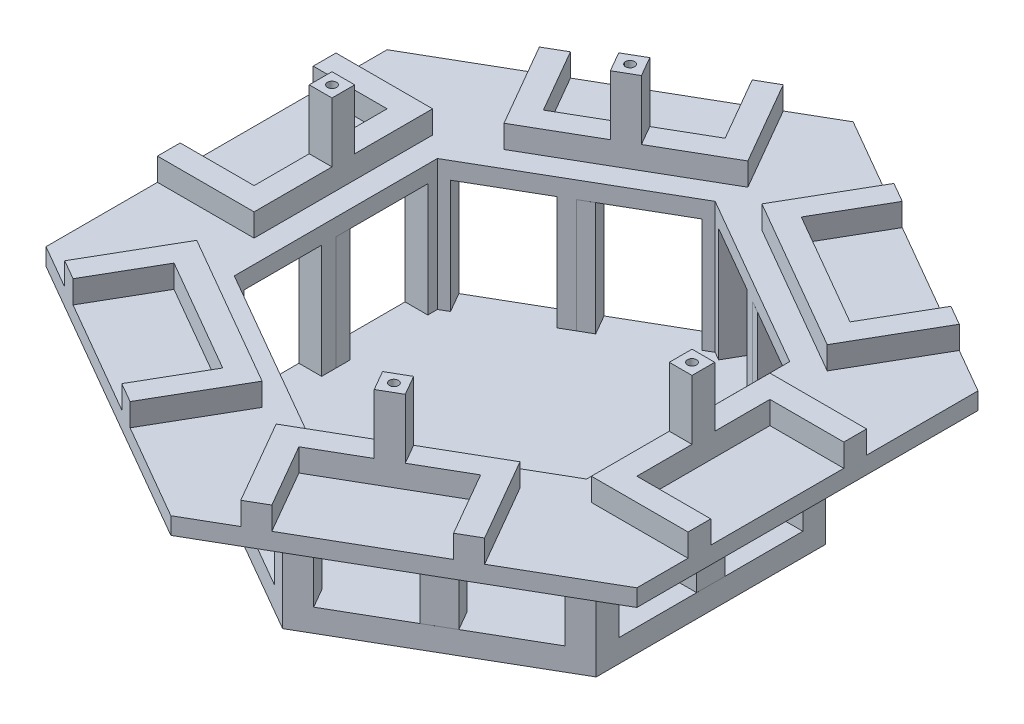
SolidWorks part; units mm, degrees
ref_plane "Front Plane" through (0, 0, 0) normal (0, 0, 1) x (1, 0, 0)
ref_plane "Top Plane" through (0, 0, 0) normal (0, 1, 0) x (1, 0, 0)
ref_plane "Right Plane" through (0, 0, 0) normal (1, 0, 0) x (0, 0, -1)
sketch "Sketch1" plane through (0, 0, 0) normal (0, 1, 0) x (1, 0, 0)
  line L1 (0, 60) -> (-51.9615, 30)
  line L2 (-51.9615, 30) -> (-51.9615, -30)
  line L3 (-51.9615, -30) -> (0, -60)
  line L4 (0, -60) -> (51.9615, -30)
  line L5 (51.9615, -30) -> (51.9615, 30)
  line L6 (51.9615, 30) -> (0, 60)
  circle A0 centre (0, 0) radius 51.9615 construction
extrude "Boss-Extrude1" add sketch "Sketch1" along normal blind 3
sketch "Sketch2" plane through (0, 3, 0) normal (0, 1, 0) x (1, 0, 0)
  line L0 (35.6673, 19.7776) -> (44.1673, 34.5)
  line L1 (51.9615, 30) -> (0, 60) construction
  line L2 (19.4808, 33.7417) -> (34.2032, 25.2417)
  line L3 (19.4808, 33.7417) -> (13.9382, 36.9417)
  line L4 (13.9382, 36.9417) -> (20.4382, 48.2)
  line L5 (34.2032, 25.2417) -> (40.7032, 36.5)
  line L7 (17.4808, 30.2776) -> (35.6673, 19.7776)
  line L8 (17.4808, 30.2776) -> (8.4741, 35.4776)
  line L9 (8.4741, 35.4776) -> (16.9741, 50.2)
  line L10 (16.9741, 50.2) -> (20.4382, 48.2)
  line L11 (40.7032, 36.5) -> (44.1673, 34.5)
  line L12 (51.9615, -17) -> (51.9615, -21)
  line L13 (34.9615, -21) -> (51.9615, -21)
  line L14 (34.9615, 0) -> (34.9615, -21)
  line L15 (34.9615, 0) -> (34.9615, 10.4)
  line L16 (34.9615, 10.4) -> (51.9615, 10.4)
  line L17 (51.9615, 10.4) -> (51.9615, 6.4)
  line L18 (38.9615, 6.4) -> (51.9615, 6.4)
  line L19 (38.9615, 0) -> (38.9615, 6.4)
  line L20 (38.9615, 0) -> (38.9615, -17)
  line L21 (38.9615, -17) -> (51.9615, -17)
  line L22 (11.2583, -53.5) -> (7.7942, -55.5)
  line L23 (-0.7058, -40.7776) -> (7.7942, -55.5)
  line L24 (17.4808, -30.2776) -> (-0.7058, -40.7776)
  line L25 (17.4808, -30.2776) -> (26.4874, -25.0776)
  line L26 (26.4874, -25.0776) -> (34.9874, -39.8)
  line L27 (34.9874, -39.8) -> (31.5233, -41.8)
  line L28 (25.0233, -30.5417) -> (31.5233, -41.8)
  line L29 (19.4808, -33.7417) -> (25.0233, -30.5417)
  line L30 (19.4808, -33.7417) -> (4.7583, -42.2417)
  line L31 (4.7583, -42.2417) -> (11.2583, -53.5)
  line L32 (-40.7032, -36.5) -> (-44.1673, -34.5)
  line L33 (-35.6673, -19.7776) -> (-44.1673, -34.5)
  line L34 (-17.4808, -30.2776) -> (-35.6673, -19.7776)
  line L35 (-17.4808, -30.2776) -> (-8.4741, -35.4776)
  line L36 (-8.4741, -35.4776) -> (-16.9741, -50.2)
  line L37 (-16.9741, -50.2) -> (-20.4382, -48.2)
  line L38 (-13.9382, -36.9417) -> (-20.4382, -48.2)
  line L39 (-19.4808, -33.7417) -> (-13.9382, -36.9417)
  line L40 (-19.4808, -33.7417) -> (-34.2032, -25.2417)
  line L41 (-34.2032, -25.2417) -> (-40.7032, -36.5)
  line L42 (-51.9615, 17) -> (-51.9615, 21)
  line L43 (-34.9615, 21) -> (-51.9615, 21)
  line L44 (-34.9615, 0) -> (-34.9615, 21)
  line L45 (-34.9615, 0) -> (-34.9615, -10.4)
  line L46 (-34.9615, -10.4) -> (-51.9615, -10.4)
  line L47 (-51.9615, -10.4) -> (-51.9615, -6.4)
  line L48 (-38.9615, -6.4) -> (-51.9615, -6.4)
  line L49 (-38.9615, 0) -> (-38.9615, -6.4)
  line L50 (-38.9615, 0) -> (-38.9615, 17)
  line L51 (-38.9615, 17) -> (-51.9615, 17)
  line L52 (-11.2583, 53.5) -> (-7.7942, 55.5)
  line L53 (0.7058, 40.7776) -> (-7.7942, 55.5)
  line L54 (-17.4808, 30.2776) -> (0.7058, 40.7776)
  line L55 (-17.4808, 30.2776) -> (-26.4874, 25.0776)
  line L56 (-26.4874, 25.0776) -> (-34.9874, 39.8)
  line L57 (-34.9874, 39.8) -> (-31.5233, 41.8)
  line L58 (-25.0233, 30.5417) -> (-31.5233, 41.8)
  line L59 (-19.4808, 33.7417) -> (-25.0233, 30.5417)
  line L60 (-19.4808, 33.7417) -> (-4.7583, 42.2417)
  line L61 (-4.7583, 42.2417) -> (-11.2583, 53.5)
  point P65 (0, 0)
  dimension "D1" = 4
  dimension "D2" = 6
extrude "Boss-Extrude2" add sketch "Sketch2" along normal blind 4
sketch "Sketch5" plane through (0, 7, 0) normal (0, 1, 0) x (1, 0, 0)
  line L18 (34.9615, -3.3) -> (34.9615, -7.3)
  line L19 (34.9615, -7.3) -> (38.9615, -7.3)
  line L20 (38.9615, -3.3) -> (38.9615, -7.3)
  line L21 (34.9615, -3.3) -> (38.9615, -3.3)
  line L22 (14.6229, -31.9276) -> (11.1588, -33.9276)
  line L23 (11.1588, -33.9276) -> (13.1588, -37.3917)
  line L24 (16.6229, -35.3917) -> (13.1588, -37.3917)
  line L25 (14.6229, -31.9276) -> (16.6229, -35.3917)
  line L30 (-34.9615, 3.3) -> (-34.9615, 7.3)
  line L31 (-34.9615, 7.3) -> (-38.9615, 7.3)
  line L32 (-38.9615, 3.3) -> (-38.9615, 7.3)
  line L33 (-34.9615, 3.3) -> (-38.9615, 3.3)
  line L34 (-14.6229, 31.9276) -> (-11.1588, 33.9276)
  line L35 (-11.1588, 33.9276) -> (-13.1588, 37.3917)
  line L36 (-16.6229, 35.3917) -> (-13.1588, 37.3917)
  line L37 (-14.6229, 31.9276) -> (-16.6229, 35.3917)
  point P31 (0, 0)
extrude "Boss-Extrude3" add sketch "Sketch5" along normal blind 10.5
sketch "Sketch7" plane through (0, 0, 0) normal (0, -1, 0) x (1, 0, 0)
  circle A0 centre (22.7308, 39.3708) radius 2.4
  circle A1 centre (45.4615, 0) radius 2.4
  circle A2 centre (22.7308, -39.3708) radius 2.4
  circle A3 centre (-22.7308, -39.3708) radius 2.4
  circle A4 centre (-45.4615, 0) radius 2.4
  circle A5 centre (-22.7308, 39.3708) radius 2.4
  point P15 (0, 0)
  dimension "D1" = 6
extrude "Boss-Extrude4" add sketch "Sketch7" along normal blind 3
sketch "Sketch9" plane through (0, 17.5, 0) normal (0, 1, 0) x (1, 0, 0)
  circle A0 centre (-36.9615, 5.3) radius 0.8
  circle A1 centre (-13.8908, 34.6596) radius 0.8
  circle A2 centre (23.0707, 29.3596) radius 0.8
  circle A3 centre (36.9615, -5.3) radius 0.8
  circle A4 centre (13.8908, -34.6596) radius 0.8
  circle A5 centre (-23.0707, -29.3596) radius 0.8
  point P14 (0, 0)
  dimension "D1" = 6
extrude "Cut-Extrude6" cut sketch "Sketch9" against normal blind 5
sketch "Sketch22" plane through (0, 0, 0) normal (0, -1, 0) x (1, 0, 0)
  line L0 (-34.9484, 20.2078) -> (-34.9746, -20.1623)
  line L1 (0.0263, 40.3701) -> (-34.9484, 20.2078)
  line L2 (34.9746, 20.1623) -> (0.0263, 40.3701)
  line L3 (34.9484, -20.2078) -> (34.9746, 20.1623)
  line L5 (-34.9746, -20.1623) -> (-0.0263, -40.3701)
  line L6 (-0.0263, -40.3701) -> (34.9484, -20.2078)
  point P17 (0, 0)
  dimension "D1" = 6
extrude "Boss-Extrude10" add sketch "Sketch22" along normal blind 24
sketch "Sketch23" plane through (0, 3, 0) normal (0, 1, 0) x (1, 0, 0)
  line L0 (-0.0233, 35.7513) -> (-30.9731, 17.8555)
  line L1 (-30.9731, 17.8555) -> (-30.9499, -17.8958)
  line L2 (-30.9499, -17.8958) -> (0.0233, -35.7513)
  line L3 (0.0233, -35.7513) -> (30.9731, -17.8555)
  line L4 (30.9731, -17.8555) -> (30.9499, 17.8958)
  line L5 (30.9499, 17.8958) -> (-0.0233, 35.7513)
extrude "Cut-Extrude7" cut sketch "Sketch23" against normal blind 23
sketch "Sketch24" plane through (34.9615, 0, -0.0228) normal (1, 0, -0.0007) x (-0.0007, 0, -1)
  line L0 (-16.185, 0) -> (16.185, 0)
  line L7 (16.185, 0) -> (16.185, -20)
  line L8 (-16.185, -20) -> (16.185, -20)
  line L9 (-16.185, 0) -> (-16.185, -20)
extrude "Cut-Extrude10" cut sketch "Sketch24" against normal blind 24 and the other way through all
ref_axis "Axis1" through (0, 0, 0) along (0, 1, 0)
pattern_circular "CirPattern1" count 6 every 60 about axis through (0, 0, 0) along (0, 1, 0) of "Cut-Extrude10"
sketch "Sketch25" plane through (0, -20, 0) normal (0, 1, 0) x (1, 0, 0)
  line L1 (0.0233, -35.7513) -> (30.9731, -17.8555) construction
  line L2 (26.4874, -25.0776) -> (14.6229, -31.9276) construction
  line L3 (15.4982, -26.8034) -> (17.6625, -25.552)
  line L4 (17.6625, -25.552) -> (19.6655, -29.0162)
  line L5 (15.3309, -31.5188) -> (19.6655, -29.0162)
  line L6 (13.3323, -28.052) -> (15.3309, -31.5188)
  line L7 (15.4982, -26.8034) -> (13.3323, -28.052)
extrude "Boss-Extrude11" add sketch "Sketch25" along normal blind 20
pattern_circular "CirPattern2" count 6 every 60 about axis through (0, 0, 0) along (0, 1, 0) of "Boss-Extrude11"
